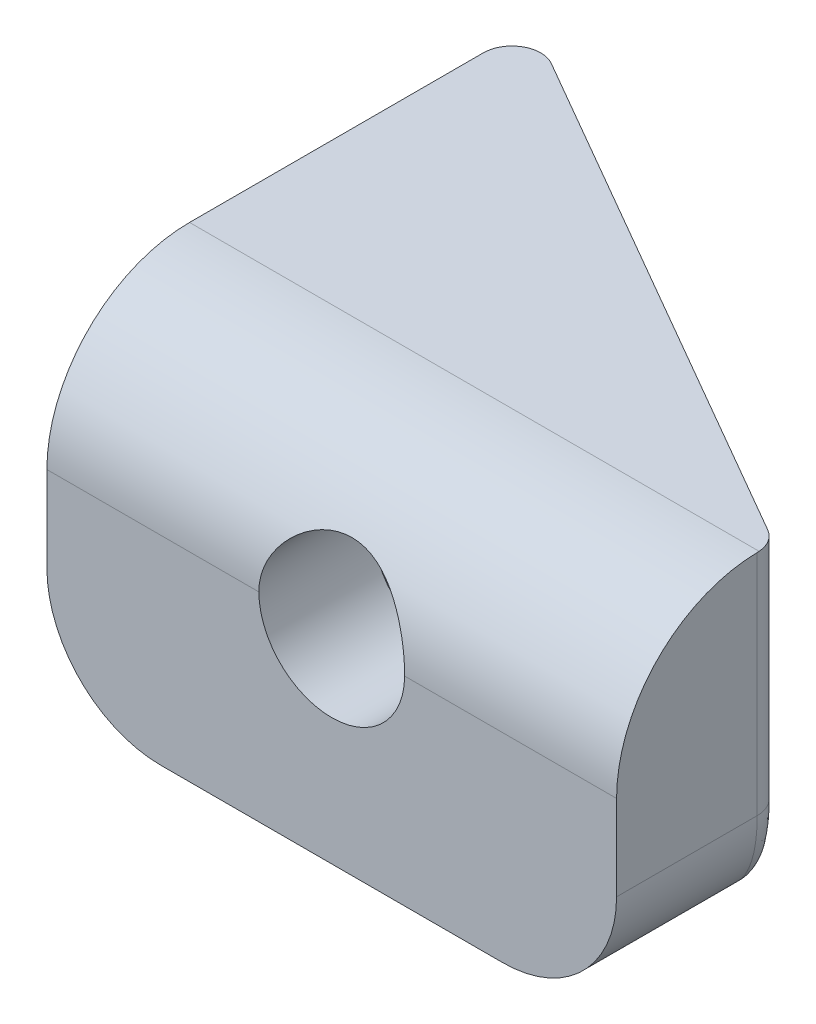
SolidWorks part; units mm, degrees
material "ASTM A36 Steel"
ref_plane "Front Plane" through (0, 0, 0) normal (0, 0, 1) x (1, 0, 0)
ref_plane "Top Plane" through (0, 0, 0) normal (0, 1, 0) x (1, 0, 0)
ref_plane "Right Plane" through (0, 0, 0) normal (1, 0, 0) x (0, 0, -1)
sketch "Sketch3" plane through (0, 0, 0) normal (1, 0, 0) x (0, 0, -1)
  line L0 (-19.05, 1.5748) -> (-19.05, -9.525)
  line L1 (-19.05, -9.525) -> (19.05, -9.525)
  line L2 (19.05, -9.525) -> (19.05, -7.9248)
  line L5 (-11.0998, 9.525) -> (19.05, 9.525)
  line L6 (19.05, 9.525) -> (19.05, -7.9248)
  line L7 (-19.05, 0) -> (19.05, 0) construction
  line L8 (0, -9.525) -> (0, 9.525) construction
  arc A0 (-11.0998, 9.525) -> (-19.05, 1.5748) centre (-11.0998, 1.5748) ccw
  point P0 (0, 0)
  dimension "D1" = 1.6002
  dimension "D3" = 38.1
  dimension "D5" = 7.9502
  dimension "D6" = 19.05
extrude "Boss-Extrude2" add sketch "Sketch3" along normal mid plane 31.75
fillet "Fillet2" radius 6.35 2 edges at (-15.875, -9.525, 0) (15.875, -9.525, 0)
sketch "Sketch4" plane through (0, 0, 0) normal (1, 0, 0) x (0, 0, -1)
  line L0 (-19.05, 5.6642) -> (-12.7, 5.6642)
  line L1 (-19.05, 1.5748) -> (-19.05, -3.175) construction
  line L2 (-12.7, 5.6642) -> (-12.7, 7.3152)
  line L3 (-12.7, 7.3152) -> (19.05, 7.3152)
  line L4 (19.05, 7.3152) -> (19.05, 1.6002)
  line L5 (19.05, 1.6002) -> (-19.05, 1.6002)
  line L6 (-19.05, 1.6002) -> (-19.05, 5.6642)
  line L9 (19.05, 9.525) -> (-11.0998, 9.525) construction
  line L10 (-8.7376, 7.3152) -> (-8.7376, 1.6002) construction
  line L11 (19.05, -3.175) -> (19.05, 9.525) construction
  point P4 (0, 0)
  point P17 (3.6148, 9.525)
  dimension "D1" = 4.064
  dimension "D2" = 6.35
  dimension "D3" = 5.715
  dimension "D4" = 7.9248
  dimension "D5" = 3.9624
revolve "Cut-Revolve2" cut sketch "Sketch4" angle 360 about L5
sketch "Sketch5" plane through (0, -9.525, 0) normal (0, -1, 0) x (1, 0, 0)
  line L0 (15.875, 10.287) -> (-15.875, -8.0439)
  line L3 (-15.875, -8.0439) -> (-15.875, -19.05)
  line L4 (-15.875, -19.05) -> (15.875, -19.05)
  line L5 (15.875, -19.05) -> (15.875, 10.287)
  line L7 (9.525, -19.05) -> (-9.525, -19.05) construction
  line L9 (15.875, 11.0998) -> (-15.875, 11.0998) construction
  line L10 (-15.875, -19.05) -> (-15.875, 19.05) construction
  line L11 (15.875, 19.05) -> (15.875, -19.05) construction
  point P14 (15.875, 6.3675)
  dimension "D1" = 60
  dimension "D2" = 0.8128
extrude "Cut-Extrude1" cut sketch "Sketch5" against normal through all both and the other way through all
fillet "Fillet1" radius 1.6002 5 edges at (14.0151, -7.6651, 9.2132) (0, -9.525, 1.1216) (-14.0151, -7.6651, -6.9701)
